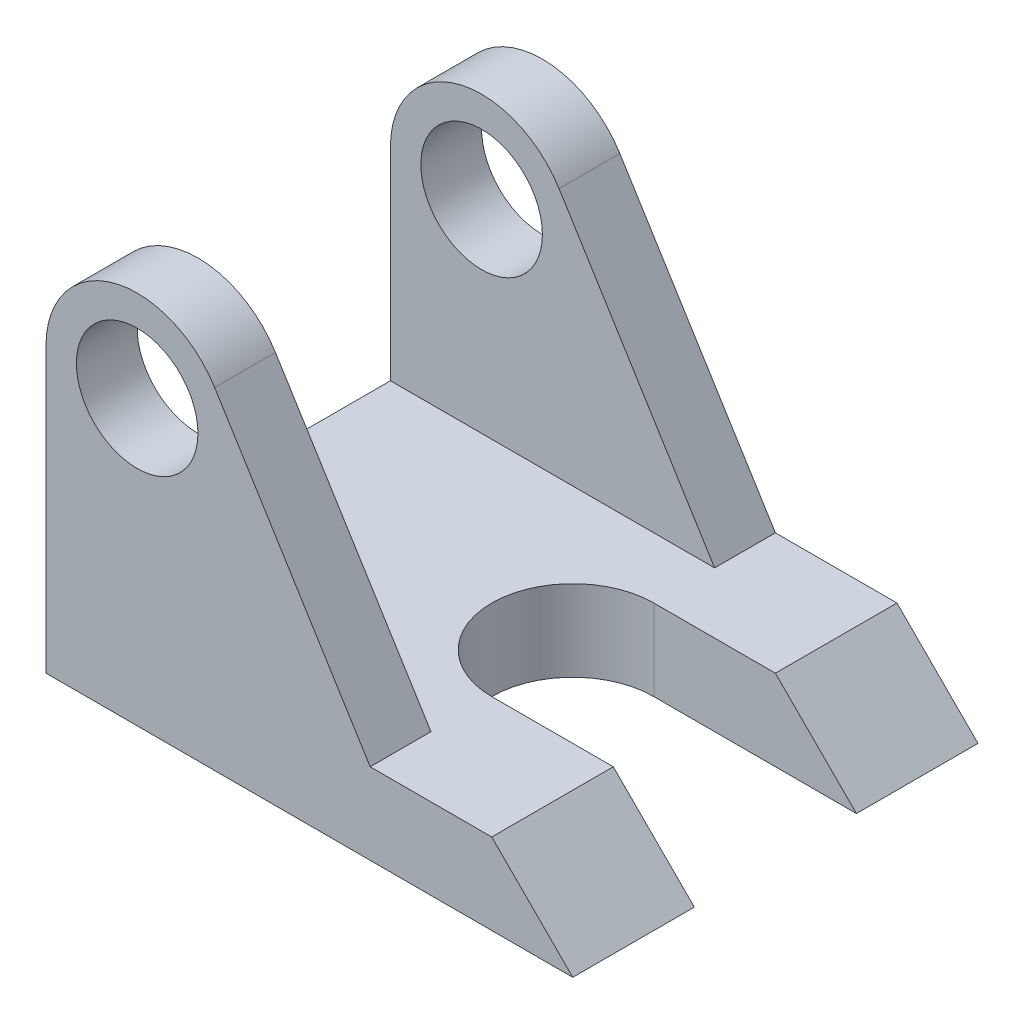
SolidWorks part; units mm, degrees
ref_plane "Front Plane" through (0, 0, 0) normal (0, 0, 1) x (1, 0, 0)
ref_plane "Top Plane" through (0, 0, 0) normal (0, 1, 0) x (1, 0, 0)
ref_plane "Right Plane" through (0, 0, 0) normal (1, 0, 0) x (0, 0, -1)
sketch "Sketch1" plane through (0, 0, 0) normal (0, 0, 1) x (1, 0, 0)
  line L0 (0, 20) -> (110, 20)
  line L1 (110, 20) -> (130, 0)
  line L2 (130, 0) -> (0, 0)
  line L3 (0, 0) -> (0, 20)
  line L4 (0, 20) -> (0, 70)
  line L5 (41.6192, 81.862) -> (80, 20)
  arc A0 (0, 70) -> (41.6192, 81.862) centre (22.5, 70) cw
  circle A1 centre (22.5, 70) radius 15
  point P9 (0, 0)
  point P10 (0, 0)
  point P11 (0, 0)
  point P13 (73.8209, 20)
  dimension "D6" = 30
  dimension "D7" = 20
  dimension "D1" = 130
  dimension "D2" = 20
  dimension "D3" = 30
  dimension "D4" = 70
  dimension "D5" = 22.5
extrude "Boss-Extrude1" add sketch "Sketch1" along normal mid plane 100 contours L3 L2 L1 L0 region at (60.1389, 9.7222, 0)
extrude "Boss-Extrude2" add sketch "Sketch1<3>" against normal blind 15 from offset 35 contours A0 L4 L0 L5 A1 region at (32.6557, 46.1421, 0) offset against normal yes
sketch "Sketch1<3>" plane through (0, 0, 0) normal (0, 0, 1) x (1, 0, 0) same geometry as "Sketch1"
mirror "Mirror2" about plane through (0, 0, 0) normal (0, 0, 1) of "Boss-Extrude2"
sketch "Sketch2" plane through (0, 0, 0) normal (0, 1, 0) x (1, 0, 0)
  line L0 (130, 20) -> (80, 20)
  line L1 (130, -50) -> (130, 50) construction
  line L2 (80, -20) -> (130, -20)
  line L3 (130, 20) -> (130, -20)
  arc A0 (80, 20) -> (80, -20) centre (80, 0) ccw
  point P6 (130, 0)
  dimension "D1" = 20
  dimension "D2" = 50
extrude "Cut-Extrude1" cut sketch "Sketch2" against normal through all both and the other way through all
